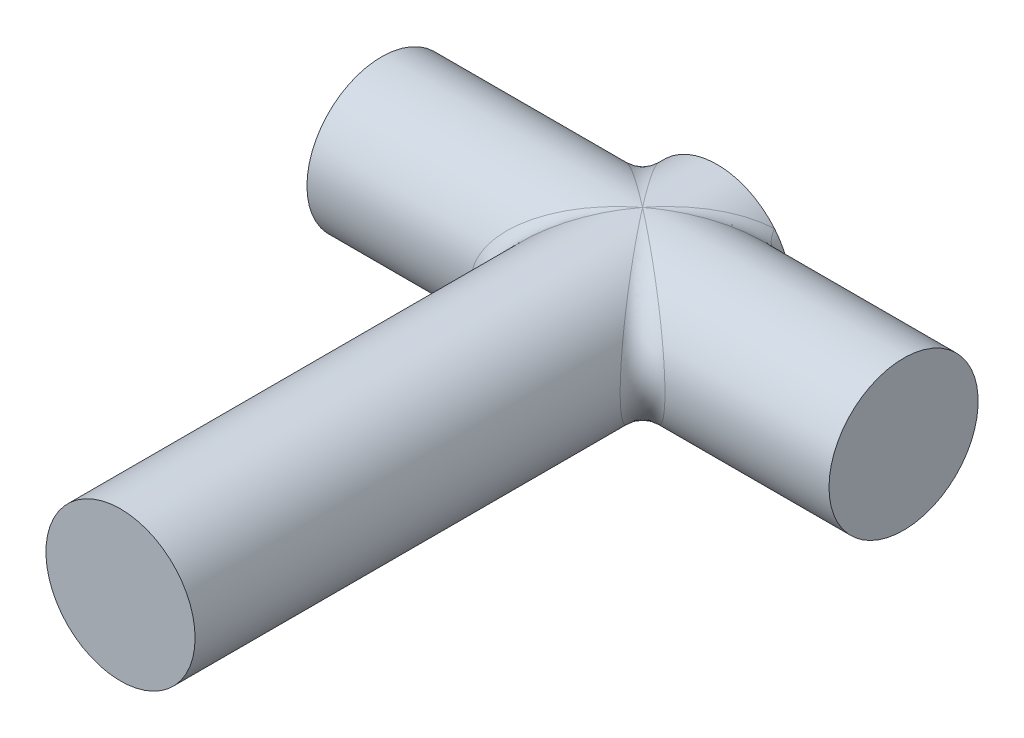
SolidWorks part; units mm, degrees
ref_plane "Front Plane" through (0, 0, 0) normal (0, 0, 1) x (1, 0, 0)
ref_plane "Top Plane" through (0, 0, 0) normal (0, 1, 0) x (1, 0, 0)
ref_plane "Right Plane" through (0, 0, 0) normal (1, 0, 0) x (0, 0, -1)
sketch "Sketch1" plane through (0, 0, 0) normal (0, 0, 1) x (1, 0, 0)
  line L0 (0, 0) -> (0, 18.9216) construction
  line L1 (8.1112, 2.951) -> (10.7093, 4.451)
  line L2 (1.5, 8.5) -> (-1.5, 8.5)
  line L3 (1.5, 8.5) -> (1.5, 11.5)
  line L4 (1.5, 11.5) -> (-1.5, 11.5)
  line L5 (-1.5, 8.5) -> (-1.5, 11.5)
  line L6 (8.1112, 2.951) -> (6.6112, 5.549)
  line L7 (6.6112, 5.549) -> (9.2093, 7.049)
  line L8 (10.7093, 4.451) -> (9.2093, 7.049)
  line L9 (0, 0) -> (16.3866, 9.4608) construction
  line L10 (6.6112, -5.549) -> (9.2093, -7.049)
  line L11 (6.6112, -5.549) -> (8.1112, -2.951)
  line L12 (8.1112, -2.951) -> (10.7093, -4.451)
  line L13 (9.2093, -7.049) -> (10.7093, -4.451)
  line L14 (0, 0) -> (16.3866, -9.4608) construction
  line L15 (-1.5, -8.5) -> (-1.5, -11.5)
  line L16 (-1.5, -8.5) -> (1.5, -8.5)
  line L17 (1.5, -8.5) -> (1.5, -11.5)
  line L18 (-1.5, -11.5) -> (1.5, -11.5)
  line L19 (0, 0) -> (0, -18.9216) construction
  line L20 (-8.1112, -2.951) -> (-10.7093, -4.451)
  line L21 (-8.1112, -2.951) -> (-6.6112, -5.549)
  line L22 (-6.6112, -5.549) -> (-9.2093, -7.049)
  line L23 (-10.7093, -4.451) -> (-9.2093, -7.049)
  line L24 (0, 0) -> (-16.3866, -9.4608) construction
  line L25 (-6.6112, 5.549) -> (-9.2093, 7.049)
  line L26 (-6.6112, 5.549) -> (-8.1112, 2.951)
  line L27 (-8.1112, 2.951) -> (-10.7093, 4.451)
  line L28 (-9.2093, 7.049) -> (-10.7093, 4.451)
  line L29 (0, 0) -> (-16.3866, 9.4608) construction
  circle A0 centre (0, 0) radius 10
  point P3 (0, 10)
  point P9 (0, 11.5)
  point P38 (0, 0)
  dimension "D1" = 20
  dimension "D2" = 1.5
  dimension "D3" = 3
  dimension "D4" = 6
extrude "Boss-Extrude1" add sketch "Sketch1" along normal blind 80 contours L7 A0 L3 L2 L5 L25 L26 L27 L20 L21 L22 L15 L16 L17 L10 L11 L12 L1 L6 | L25 A0 L27 L26 | L20 A0 L22 L21 | L15 A0 L17 L16 | L1 A0 L7 L6 | L3 A0 L5 L2 | L10 A0 L12 L11 region at (7.9948, 4.6158, 0) region at (0, 0, 0) region at (7.9948, -4.6158, 0) region at (0, 9.2316, 0) region at (0, -9.2316, 0) region at (-7.9948, 4.6158, 0) region at (-7.9948, -4.6158, 0)
ref_plane "Plane1" through (0, 0, 10) normal (0, 0, -1) x (-1, 0, 0)
sketch "Sketch3" plane through (0, 0, 10) normal (0, 0, -1) x (-1, 0, 0)
  line L0 (0, 0) -> (-24.7187, 0) construction
  line L1 (-35, 10) -> (0, 10)
  line L2 (-35, 10) -> (-35, 0)
  line L3 (-35, 0) -> (0, 0)
  line L4 (0, 10) -> (0, 0)
  circle A0 centre (0, 0) radius 10 construction
  point P8 (-10, 0)
  dimension "D1" = 10
  dimension "D2" = 25
revolve "Revolve1" add sketch "Sketch3" angle 360 about L0
mirror "Mirror1" about plane through (0, 0, 0) normal (1, 0, 0) of "Revolve1"
fillet "Fillet1" radius 3 6 edges at (-10, 0, 20) (7.0711, -7.0711, 2.9289) (-7.0711, -7.0711, 2.9289) (-7.0711, 7.0711, 2.9289) (7.0711, 7.0711, 2.9289) (10, 0, 20)
